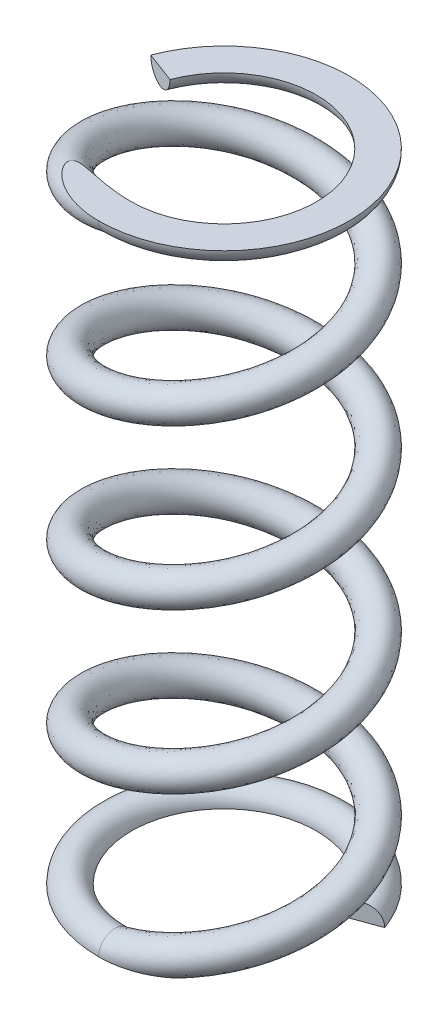
SolidWorks part; units mm, degrees
note: '?' marks a value the reader was unsure of. The reader was unsure of these and kept them because the rebuilt part matched: shared geometry of "Sketch5<5>".
ref_plane "Front" through (0, 0, 0) normal (0, 0, 1) x (1, 0, 0)
ref_plane "Top" through (0, 0, 0) normal (0, 1, 0) x (1, 0, 0)
ref_plane "Right" through (0, 0, 0) normal (1, 0, 0) x (0, 0, -1)
ref_plane "Top Shock" through (0, 127, 0) normal (0, 1, 0) x (1, 0, 0)
ref_axis "Axis1" through (0, 129.1224, 0) along (0, -1, 0)?
sketch "Cut" plane through (0, 0, 0) normal (0, 0, 1) x (1, 0, 0)
  line L0 (50, 127) -> (-50, 127) construction
  line L1 (-48.567, 150.0825) -> (54.9841, 150.0825)
  line L2 (-48.567, 150.0825) -> (-48.567, 127)
  line L3 (-48.567, 127) -> (54.9841, 127)
  line L4 (54.9841, 150.0825) -> (54.9841, 127)
  line L5 (50, 0) -> (-50, 0) construction
  line L6 (-48.567, 0) -> (54.9841, 0)
  line L7 (-48.567, 0) -> (-48.567, -30.0736)
  line L8 (-48.567, -30.0736) -> (54.9841, -30.0736)
  line L9 (54.9841, 0) -> (54.9841, -30.0736)
sketch "Helix" plane through (0, 0, 0) normal (0, 1, 0) x (1, 0, 0)
  line L0 (0, 0) -> (0, -21.717) construction
  circle A0 centre (0, 0) radius 21.717
  point P3 (0, -26.36)
  dimension "D1" = 21.717
sketch "Sketch3" plane through (0, 0, 0) normal (0, 1, 0) x (1, 0, 0)
  line L0 (0, 0) -> (23.2292, 8.4547) construction
  line L2 (0, 0) -> (0, -24.72) construction
  arc A0 (23.2292, 8.4547) -> (0, -24.72) centre (0, 0) ccw
  point P3 (0, -28)
  dimension "D1" = 24.72
  dimension "D2" = 110
sketch "Sketch5" plane through (0, 0, 0) normal (1, 0, 0) x (0, 0, -1)
  line L0 (-24.997, 0) -> (0, 0) construction
  circle A0 centre (-21.717, 0) radius 3.28
  dimension "D1" = 6.56
  dimension "D2" = 21.717
sketch "Sketch6" plane through (0, 127, 0) normal (0, 1, 0) x (1, 0, 0)
  line L0 (0, -0.5556) -> (0, -21.717) construction
  line L1 (0, -0.5556) -> (-20.323, 7.6554) construction
  arc A0 (0, -21.717) -> (-20.323, 7.6554) centre (0, 0) ccw
  point P3 (0, -21.717)
  dimension "D1" = 21.717
  dimension "D2" = 112
sketch "Sketch7" plane through (0, 0, 0) normal (1, 0, 0) x (0, 0, -1)
  circle A0 centre (-21.717, 127) radius 3.28
curve "Helix/Spiral3" pitch 31.75 height 127 turns 4
sweep "Sweep7" add profiles "Sketch5" path "Helix/Spiral3"
sweep "Sweep8" add profiles "Sketch5<5>" path "Sketch3"
sketch "Sketch5<5>" plane through (0, 0, 0) normal (1, 0, 0) x (0, 0, -1) same geometry as "Sketch5"
sweep "Sweep9" add profiles "Sketch7" path "Sketch6"
extrude "Cut-Extrude3" cut sketch "Cut" against normal through all both and the other way through all
sketch "Sketch9" plane through (0, 0, 0) normal (0, -1, 0) x (1, 0, 0)
  circle A0 centre (0, 0) radius 21.44 construction
